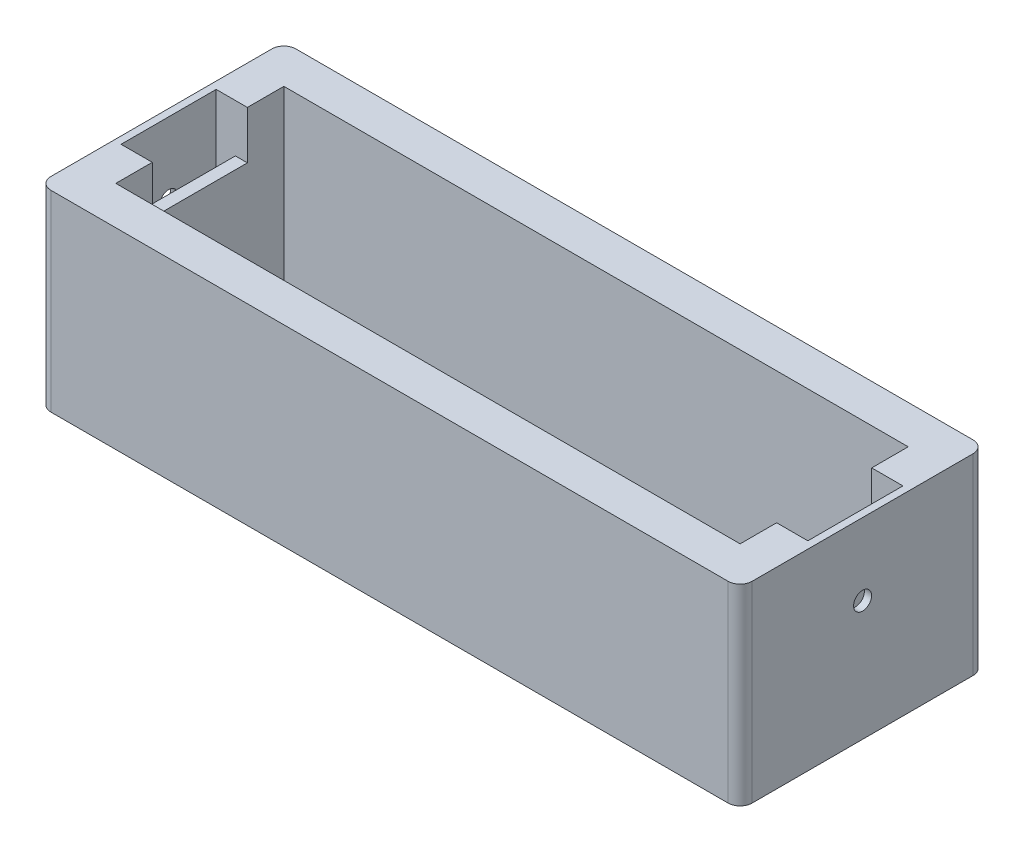
SolidWorks part; units mm, degrees
ref_plane "Front Plane" through (0, 0, 0) normal (0, 0, 1) x (1, 0, 0)
ref_plane "Top Plane" through (0, 0, 0) normal (0, 1, 0) x (1, 0, 0)
ref_plane "Right Plane" through (0, 0, 0) normal (1, 0, 0) x (0, 0, -1)
sketch "Sketch2" plane through (0, 0, 0) normal (0, 1, 0) x (1, 0, 0)
  line L1 (-29.2, -10.2) -> (29.2, -10.2)
  line L2 (-29.2, -10.2) -> (-29.2, 10.2)
  line L3 (-29.2, 10.2) -> (29.2, 10.2)
  line L4 (29.2, -10.2) -> (29.2, 10.2)
  line L5 (-29.2, -10.2) -> (29.2, 10.2) construction
  line L6 (-29.2, 10.2) -> (29.2, -10.2) construction
  point P0 (0, 0)
  dimension "D1" = 58.4
  dimension "D2" = 20.4
extrude "Boss-Extrude1" add sketch "Sketch2" along normal blind 16
sketch "Sketch3" plane through (0, 16, 0) normal (0, 1, 0) x (1, 0, 0)
  line L0 (29.2, -10.2) -> (29.2, 10.2) construction
  line L1 (-26, 7) -> (26, 7)
  line L2 (-26, 7) -> (-26, -7)
  line L3 (-26, -7) -> (26, -7)
  line L4 (26, 7) -> (26, -7)
  line L5 (-26, 7) -> (26, -7) construction
  line L6 (-26, -7) -> (26, 7) construction
  line L7 (-29.2, -10.2) -> (29.2, -10.2) construction
  point P0 (0, 0)
  dimension "D1" = 3.2
  dimension "D2" = 3.2
extrude "Cut-Extrude1" cut sketch "Sketch3" against normal offset from surface (14 mm away) 2 up to face at (0, 0, 0)
fillet "Fillet1" radius 1 4 edges at (-29.2, 8, -10.2) (29.2, 8, -10.2) (29.2, 8, 10.2) (-29.2, 8, 10.2)
sketch "Sketch4" plane through (0, 16, 0) normal (0, 1, 0) x (1, 0, 0)
  line L0 (-26, 7) -> (-26, -7) construction
  line L1 (-26, 0) -> (-27, 0)
  line L2 (-26, 0) -> (-26, 3.96)
  line L3 (-26, 3.96) -> (-27, 3.96)
  line L4 (-27, 0) -> (-27, 3.96)
  dimension "D2" = 3.96
extrude "Cut-Extrude2" cut sketch "Sketch4" against normal offset from surface (4 mm away) 4 up to face at (0, 16, 0)
sketch "Sketch5" plane through (0, 16, 0) normal (0, 1, 0) x (1, 0, 0)
  line L1 (-27, 0) -> (-28.6, 0)
  line L2 (-27, 0) -> (-27, 3.96)
  line L3 (-27, 3.96) -> (-28.6, 3.96)
  line L4 (-28.6, 0) -> (-28.6, 3.96)
  dimension "D2" = 3.96
extrude "Cut-Extrude3" cut sketch "Sketch5" against normal offset from surface (12 mm away) 12 up to face at (-13.25, 16, -0.99)
mirror "Mirror4" about plane through (0, 0, 0) normal (1, 0, 0) of "Cut-Extrude3", "Cut-Extrude2"
mirror "Mirror5" about plane through (0, 0, 0) normal (0, 0, 1) of "Mirror4"
sketch "Sketch6" plane through (29.2, 0, 0) normal (1, 0, 0) x (0, 0, -1)
  line L0 (-9.2, 0) -> (9.2, 0) construction
  circle A0 centre (0, 10) radius 0.75
  dimension "D1" = 1.5
  dimension "D2" = 10
extrude "Cut-Extrude4" cut sketch "Sketch6" against normal up to next
mirror "Mirror6" about plane through (0, 0, 0) normal (1, 0, 0) of "Cut-Extrude4"
equation "\"D1@Sketch2\" = 44 + 6.4 + 8"
equation "\"D2@Sketch2\" = 10 + 6.4 + 4"
equation "\"D1@Boss-Extrude1\" = 10 + 2 + 4"
equation "\"D1@Sketch3\"= 3.2"
equation "\"D2@Sketch3\"=3.2"
equation "\"D1@Cut-Extrude1\"=2"
equation "\"D1@Fillet1\"=1"
equation "\"D2@Sketch4\"=7.92 / 2"
equation "\"D1@Sketch5\"=1.6"
equation "\"D2@Sketch5\"=7.92 / 2"
